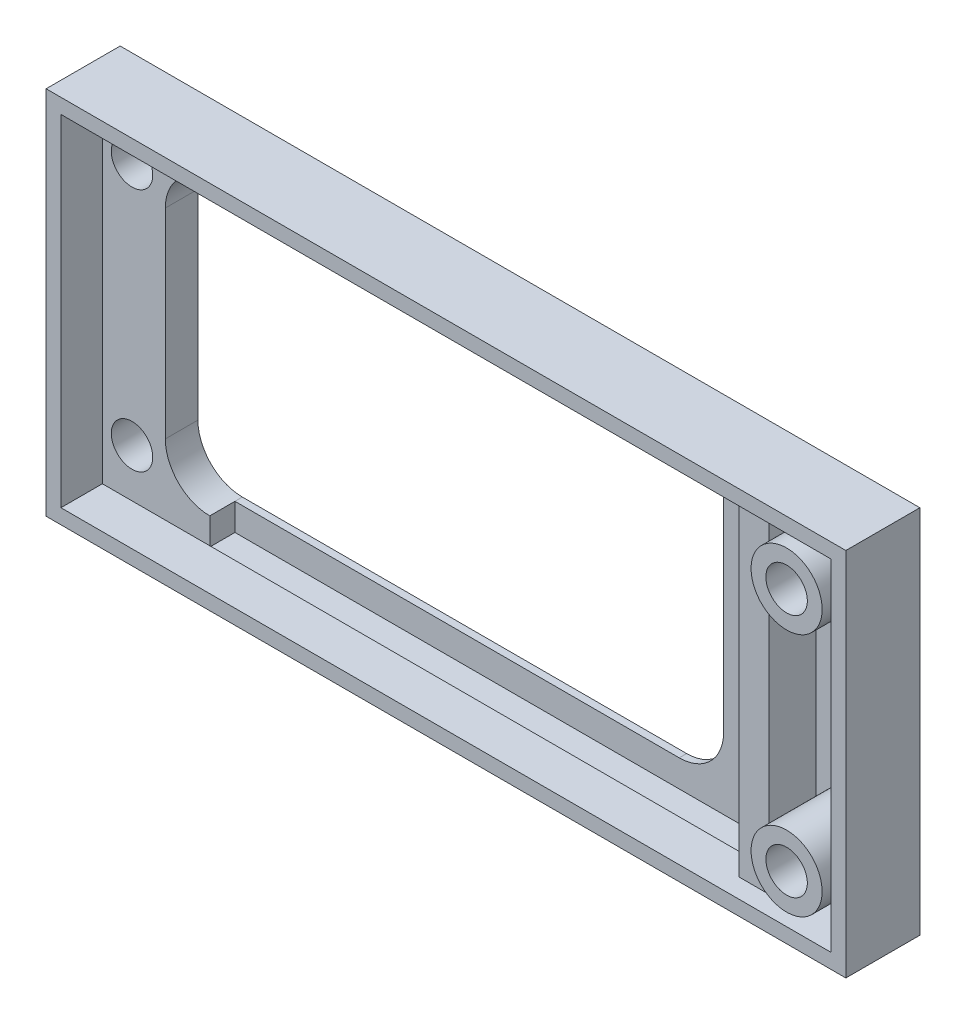
SolidWorks part; units mm, degrees
ref_plane "Front Plane" through (0, 0, 0) normal (0, 0, 1) x (1, 0, 0)
ref_plane "Top Plane" through (0, 0, 0) normal (0, 1, 0) x (1, 0, 0)
ref_plane "Right Plane" through (0, 0, 0) normal (1, 0, 0) x (0, 0, -1)
sketch "Sketch1" plane through (0, 0, 0) normal (0, 0, 1) x (1, 0, 0)
  line L1 (-26, -11.5) -> (26, -11.5)
  line L2 (-26, -11.5) -> (-26, 11.5)
  line L3 (-26, 11.5) -> (26, 11.5)
  line L4 (26, -11.5) -> (26, 11.5)
  line L5 (-26, -11.5) -> (26, 11.5) construction
  line L6 (-26, 11.5) -> (26, -11.5) construction
  line L7 (-27, -12.5) -> (27, -12.5)
  line L8 (-27, -12.5) -> (-27, 12.5)
  line L9 (-27, 12.5) -> (27, 12.5)
  line L10 (27, -12.5) -> (27, 12.5)
  line L11 (-27, -12.5) -> (27, 12.5) construction
  line L12 (-27, 12.5) -> (27, -12.5) construction
  point P0 (0, 0)
  point P6 (0, 0)
  dimension "D1" = 23
  dimension "D2" = 52
  dimension "D3" = 1
  dimension "D4" = 1
extrude "Boss-Extrude1" add sketch "Sketch1" along normal blind 5
sketch "Sketch2" plane through (0, 0, 0) normal (0, 0, -1) x (-1, 0, 0)
  line L0 (-23, 8.25) -> (-23, -8.25) construction
  line L1 (-11.25, -9.75) -> (18.75, -9.75)
  line L2 (-14.25, -6.75) -> (-14.25, 6.75)
  line L3 (-11.25, 9.75) -> (18.75, 9.75)
  line L4 (21.75, -6.75) -> (21.75, 6.75)
  line L5 (-14.25, -9.75) -> (21.75, 9.75) construction
  line L6 (-14.25, 9.75) -> (21.75, -9.75) construction
  line L7 (-27, 12.5) -> (27, 12.5) construction
  line L8 (27, -12.5) -> (-27, -12.5)
  line L9 (27, -12.5) -> (27, 12.5)
  line L10 (27, 12.5) -> (-27, 12.5)
  line L11 (-27, -12.5) -> (-27, 12.5)
  line L12 (27, -12.5) -> (-27, 12.5) construction
  line L13 (27, 12.5) -> (-27, -12.5) construction
  line L14 (-27, -12.5) -> (-27, 12.5) construction
  line L15 (26, 11.5) -> (26, -11.5) construction
  line L19 (27, 12.5) -> (27, -12.5) construction
  line L28 (27, -12.5) -> (-27, -12.5) construction
  line L29 (24, 8.25) -> (24, -8.25) construction
  arc A0 (18.75, 9.75) -> (21.75, 6.75) centre (18.75, 6.75) cw
  arc A1 (18.75, -9.75) -> (21.75, -6.75) centre (18.75, -6.75) ccw
  arc A2 (-11.25, -9.75) -> (-14.25, -6.75) centre (-11.25, -6.75) cw
  arc A3 (-14.25, 6.75) -> (-11.25, 9.75) centre (-11.25, 6.75) cw
  circle A4 centre (24, 8.25) radius 1.4
  circle A5 centre (24, -8.25) radius 1.4
  circle A6 centre (-23, 8.25) radius 1.4
  circle A7 centre (-23, -8.25) radius 1.4
  point P0 (0, 0)
  point P6 (0, 0)
  point P35 (24, 0)
  point P39 (-14.25, 0)
  point P40 (3.75, 0)
  point P44 (-23, 0)
  dimension "D3" = 3
  dimension "D4" = 2.8
  dimension "D5" = 2.8
  dimension "D6" = 2
  dimension "D7" = 2
  dimension "D8" = 36
  dimension "D9" = 16.5
  dimension "D10" = 4.25
  dimension "D11" = 4
  dimension "D12" = 16.5
  dimension "D14" = 4
  dimension "D2" = 19.5
extrude "Boss-Extrude2" add sketch "Sketch2" against normal blind 2.2
sketch "Sketch3" plane through (0, 0, 2.2) normal (0, 0, 1) x (1, 0, 0)
  line L1 (26, 11.5) -> (-18.75, 11.5)
  line L2 (26, 11.5) -> (26, -11.5719)
  line L3 (26, -11.5719) -> (-18.75, -11.5719)
  line L4 (-18.75, 11.5) -> (-18.75, -11.5719)
extrude "Cut-Extrude1" cut sketch "Sketch3" against normal blind 1.7
sketch "Sketch4" plane through (0, 0, 0.5) normal (0, 0, 1) x (1, 0, 0)
fillet "Fillet1" radius 1 1 edges at (-18.75, 10.625, 2.2)
sketch "Sketch5" plane through (0, 0, 0.5) normal (0, 0, 1) x (1, 0, 0)
  line L0 (26, 11.5) -> (-18.75, 11.5) construction
  line L1 (18.5, 11.5) -> (20.5, 11.5)
  line L2 (18.5, 11.5) -> (18.5, -11.5719)
  line L3 (18.5, -11.5719) -> (20.5, -11.5719)
  line L4 (20.5, 11.5) -> (20.5, -11.5719)
  line L5 (-18.75, -11.5719) -> (26, -11.5719) construction
  line L6 (-26, 11.5) -> (-26, -11.5) construction
  dimension "D1" = 44.5
  dimension "D2" = 2
extrude "Boss-Extrude3" add sketch "Sketch5" along normal blind 3.2
sketch "Sketch7" plane through (0, 0, 0.5) normal (0, 0, 1) x (1, 0, 0)
  circle A0 centre (23, 8.25) radius 1.4
  circle A1 centre (23, -8.25) radius 1.4
  circle A2 centre (23, -8.25) radius 2.4
  circle A3 centre (23, 8.25) radius 2.4
  dimension "D1" = 1
extrude "Boss-Extrude5" add sketch "Sketch7" along normal up to surface (4.5 mm away) up to face at (0, 0, 5)
